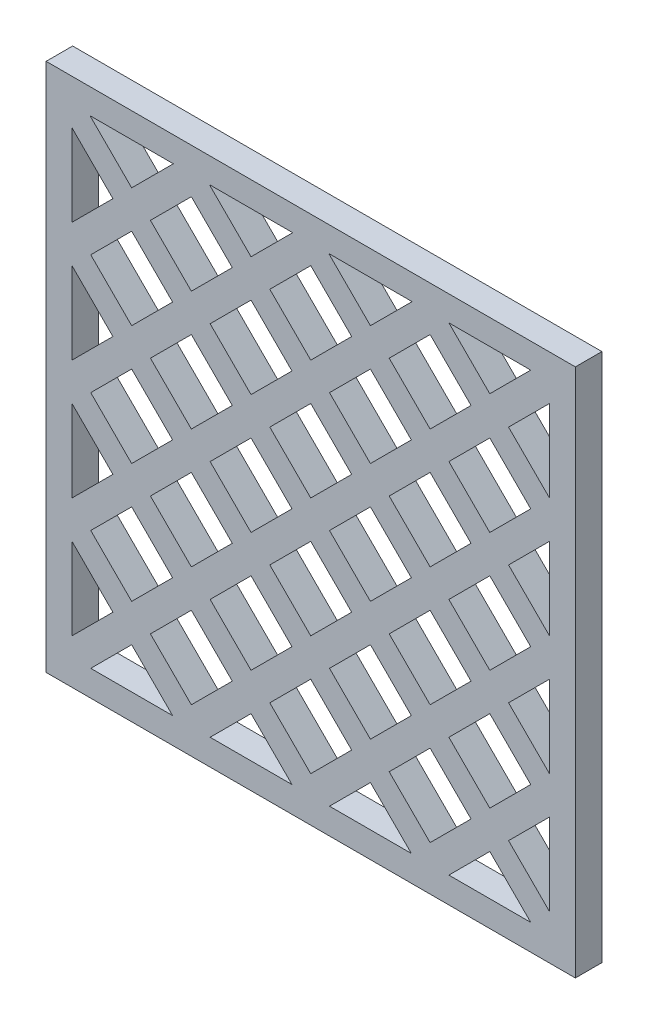
SolidWorks part; units mm, degrees
ref_plane "Front Plane" through (0, 0, 0) normal (0, 0, 1) x (1, 0, 0)
ref_plane "Top Plane" through (0, 0, 0) normal (0, 1, 0) x (1, 0, 0)
ref_plane "Right Plane" through (0, 0, 0) normal (1, 0, 0) x (0, 0, -1)
sketch "Sketch4" plane through (0, 0, 0) normal (0, 0, 1) x (1, 0, 0)
  line L0 (-16.7778, -18) -> (-10.4142, -18) construction
  line L1 (-16.6426, 18.0568) -> (-10.3574, 18.0568)
  line L2 (-18, 16.5858) -> (-18, 10.4142)
  line L3 (-16.7778, -18) -> (-10.4142, -18)
  line L5 (10.4142, -18) -> (16.5858, -18)
  line L6 (-18, -18) -> (0, 0) construction
  line L7 (-9, -18) -> (-9, -9) construction
  line L8 (-9, -9) -> (-18, -9) construction
  line L9 (-18, -10.4142) -> (-18, -16.7778) construction
  line L12 (-10.4142, -9) -> (-13.5, -12.0858)
  line L15 (-9, -10.4142) -> (-12.0858, -13.5)
  line L16 (-10.2222, -9) -> (-16.7778, -18) construction
  line L17 (-18, -16.7778) -> (-9, -10.2222) construction
  line L22 (-13.5, -13.5) -> (-13.5, -18) construction
  line L23 (-13.5, -18) -> (-13.5, -9) construction
  line L24 (-9, -13.5) -> (-18, -13.5) construction
  line L25 (-18, -13.5) -> (-13.5, -13.5) construction
  line L26 (-14.9142, -13.5) -> (-18, -16.5858)
  line L27 (-13.5, -14.9142) -> (-16.5858, -18)
  line L28 (-9, -16.5858) -> (-12.0858, -13.5)
  line L29 (-13.5, -14.9142) -> (-10.4142, -18)
  line L30 (-14.9142, -13.5) -> (-18, -10.4142)
  line L31 (-16.5858, -9) -> (-13.5, -12.0858)
  line L32 (-5.9142, -13.5) -> (-9, -10.4142)
  line L33 (-7.5858, -9) -> (-4.5, -12.0858)
  line L34 (-1.4142, -9) -> (-4.5, -12.0858)
  line L35 (0, -10.4142) -> (-3.0858, -13.5)
  line L36 (0, -16.5858) -> (-3.0858, -13.5)
  line L37 (-4.5, -14.9142) -> (-1.4142, -18)
  line L38 (-4.5, -14.9142) -> (-7.5858, -18)
  line L39 (-5.9142, -13.5) -> (-9, -16.5858)
  line L40 (3.0858, -13.5) -> (0, -10.4142)
  line L41 (1.4142, -9) -> (4.5, -12.0858)
  line L42 (7.5858, -9) -> (4.5, -12.0858)
  line L43 (9, -10.4142) -> (5.9142, -13.5)
  line L44 (9, -16.5858) -> (5.9142, -13.5)
  line L45 (4.5, -14.9142) -> (7.5858, -18)
  line L46 (4.5, -14.9142) -> (1.4142, -18)
  line L47 (3.0858, -13.5) -> (0, -16.5858)
  line L48 (12.0858, -13.5) -> (9, -10.4142)
  line L49 (10.4142, -9) -> (13.5, -12.0858)
  line L50 (16.5858, -9) -> (13.5, -12.0858)
  line L51 (18, -10.4142) -> (14.9142, -13.5)
  line L52 (18, -16.5858) -> (14.9142, -13.5)
  line L53 (13.5, -14.9142) -> (16.5858, -18)
  line L54 (13.5, -14.9142) -> (10.4142, -18)
  line L55 (12.0858, -13.5) -> (9, -16.5858)
  line L56 (-5.9142, -4.5) -> (-9, -1.4142)
  line L57 (-7.5858, 0) -> (-4.5, -3.0858)
  line L58 (-1.4142, 0) -> (-4.5, -3.0858)
  line L59 (0, -1.4142) -> (-3.0858, -4.5)
  line L60 (0, -7.5858) -> (-3.0858, -4.5)
  line L61 (-4.5, -5.9142) -> (-1.4142, -9)
  line L62 (-4.5, -5.9142) -> (-7.5858, -9)
  line L63 (-5.9142, -4.5) -> (-9, -7.5858)
  line L64 (3.0858, -4.5) -> (0, -1.4142)
  line L65 (1.4142, 0) -> (4.5, -3.0858)
  line L66 (7.5858, 0) -> (4.5, -3.0858)
  line L67 (9, -1.4142) -> (5.9142, -4.5)
  line L68 (9, -7.5858) -> (5.9142, -4.5)
  line L69 (4.5, -5.9142) -> (7.5858, -9)
  line L70 (4.5, -5.9142) -> (1.4142, -9)
  line L71 (3.0858, -4.5) -> (0, -7.5858)
  line L72 (12.0858, -4.5) -> (9, -1.4142)
  line L73 (10.4142, 0) -> (13.5, -3.0858)
  line L74 (16.5858, 0) -> (13.5, -3.0858)
  line L75 (18, -1.4142) -> (14.9142, -4.5)
  line L76 (18, -7.5858) -> (14.9142, -4.5)
  line L77 (13.5, -5.9142) -> (16.5858, -9)
  line L78 (13.5, -5.9142) -> (10.4142, -9)
  line L79 (12.0858, -4.5) -> (9, -7.5858)
  line L80 (-5.9142, 4.5) -> (-9, 7.5858)
  line L81 (-7.5858, 9) -> (-4.5, 5.9142)
  line L82 (-1.4142, 9) -> (-4.5, 5.9142)
  line L83 (0, 7.5858) -> (-3.0858, 4.5)
  line L84 (0, 1.4142) -> (-3.0858, 4.5)
  line L85 (-4.5, 3.0858) -> (-1.4142, 0)
  line L86 (-4.5, 3.0858) -> (-7.5858, 0)
  line L87 (-5.9142, 4.5) -> (-9, 1.4142)
  line L88 (3.0858, 4.5) -> (0, 7.5858)
  line L89 (1.4142, 9) -> (4.5, 5.9142)
  line L90 (7.5858, 9) -> (4.5, 5.9142)
  line L91 (9, 7.5858) -> (5.9142, 4.5)
  line L92 (9, 1.4142) -> (5.9142, 4.5)
  line L93 (4.5, 3.0858) -> (7.5858, 0)
  line L94 (4.5, 3.0858) -> (1.4142, 0)
  line L95 (3.0858, 4.5) -> (0, 1.4142)
  line L96 (12.0858, 4.5) -> (9, 7.5858)
  line L97 (10.4142, 9) -> (13.5, 5.9142)
  line L98 (16.5858, 9) -> (13.5, 5.9142)
  line L99 (18, 7.5858) -> (14.9142, 4.5)
  line L100 (18, 1.4142) -> (14.9142, 4.5)
  line L101 (13.5, 3.0858) -> (16.5858, 0)
  line L102 (13.5, 3.0858) -> (10.4142, 0)
  line L103 (12.0858, 4.5) -> (9, 1.4142)
  line L104 (-5.9142, 13.5) -> (-9, 16.5858)
  line L105 (-7.6426, 18.0568) -> (-4.5, 14.9142)
  line L106 (-1.3574, 18.0568) -> (-4.5, 14.9142)
  line L107 (0, 16.5858) -> (-3.0858, 13.5)
  line L108 (0, 10.4142) -> (-3.0858, 13.5)
  line L109 (-4.5, 12.0858) -> (-1.4142, 9)
  line L110 (-4.5, 12.0858) -> (-7.5858, 9)
  line L111 (-5.9142, 13.5) -> (-9, 10.4142)
  line L112 (3.0858, 13.5) -> (0, 16.5858)
  line L113 (1.3574, 18.0568) -> (4.5, 14.9142)
  line L114 (7.6426, 18.0568) -> (4.5, 14.9142)
  line L115 (9, 16.5858) -> (5.9142, 13.5)
  line L116 (9, 10.4142) -> (5.9142, 13.5)
  line L117 (4.5, 12.0858) -> (7.5858, 9)
  line L118 (4.5, 12.0858) -> (1.4142, 9)
  line L119 (3.0858, 13.5) -> (0, 10.4142)
  line L120 (12.0858, 13.5) -> (9, 16.5858)
  line L121 (10.4142, 18.0568) -> (13.5, 14.9711)
  line L122 (16.5858, 18.0568) -> (13.5, 14.9711)
  line L125 (13.5, 12.0858) -> (16.5858, 9)
  line L126 (13.5, 12.0858) -> (10.4142, 9)
  line L127 (12.0858, 13.5) -> (9, 10.4142)
  line L128 (-14.9142, -4.5) -> (-18, -1.4142)
  line L129 (-16.5858, 0) -> (-13.5, -3.0858)
  line L130 (-10.4142, 0) -> (-13.5, -3.0858)
  line L131 (-9, -1.4142) -> (-12.0858, -4.5)
  line L132 (-9, -7.5858) -> (-12.0858, -4.5)
  line L133 (-13.5, -5.9142) -> (-10.4142, -9)
  line L134 (-13.5, -5.9142) -> (-16.5858, -9)
  line L135 (-14.9142, -4.5) -> (-18, -7.5858)
  line L136 (-14.9142, 4.5) -> (-18, 7.5858)
  line L137 (-16.5858, 9) -> (-13.5, 5.9142)
  line L138 (-10.4142, 9) -> (-13.5, 5.9142)
  line L139 (-9, 7.5858) -> (-12.0858, 4.5)
  line L140 (-9, 1.4142) -> (-12.0858, 4.5)
  line L141 (-13.5, 3.0858) -> (-10.4142, 0)
  line L142 (-13.5, 3.0858) -> (-16.5858, 0)
  line L143 (-14.9142, 4.5) -> (-18, 1.4142)
  line L144 (-14.9142, 13.5) -> (-18, 16.5858)
  line L145 (-16.6426, 18.0568) -> (-13.5, 14.9142)
  line L146 (-10.3574, 18.0568) -> (-13.5, 14.9142)
  line L147 (-9, 16.5858) -> (-12.0858, 13.5)
  line L148 (-9, 10.4142) -> (-12.0858, 13.5)
  line L149 (-13.5, 12.0858) -> (-10.4142, 9)
  line L150 (-13.5, 12.0858) -> (-16.5858, 9)
  line L151 (-14.9142, 13.5) -> (-18, 10.4142)
  line L152 (-18, 10.4142) -> (-18, 16.5858)
  line L153 (-16.6426, 18.0568) -> (-10.3574, 18.0568)
  line L154 (-7.6426, 18.0568) -> (-1.3574, 18.0568)
  line L155 (1.3574, 18.0568) -> (7.6426, 18.0568)
  line L156 (10.4142, 18.0568) -> (16.5858, 18.0568)
  line L158 (18, 7.5858) -> (18, 1.4142)
  line L159 (18, -1.4142) -> (18, -7.5858)
  line L160 (18, -10.4142) -> (18, -16.5858)
  line L161 (0, 0) -> (16.5858, 0) construction
  line L162 (10.4142, -18) -> (16.5858, -18)
  line L163 (7.5858, -18) -> (1.4142, -18)
  line L164 (-1.4142, -18) -> (-7.5858, -18)
  line L165 (-10.4142, -18) -> (-16.7778, -18)
  line L166 (-18, -16.5858) -> (-18, -10.4142)
  line L167 (-16.5858, -18) -> (-10.4142, -18)
  line L168 (-18, -7.5858) -> (-18, -1.4142)
  line L169 (-18, 1.4142) -> (-18, 7.5858)
  line L170 (-18, 7.5858) -> (-18, 1.4142)
  line L171 (-7.6426, 18.0568) -> (-1.3574, 18.0568)
  line L172 (1.3574, 18.0568) -> (7.6426, 18.0568)
  line L173 (10.4142, 18.0568) -> (16.5858, 18.0568)
  line L174 (18, 7.5858) -> (18, 1.4142)
  line L175 (18, -10.4142) -> (18, -16.5858)
  line L176 (1.4142, -18) -> (7.5858, -18)
  line L177 (-7.5858, -18) -> (-1.4142, -18)
  line L178 (-18, -10.4142) -> (-18, -16.7778)
  line L179 (-18, -1.4142) -> (-18, -7.5858)
  line L180 (18, 16.5858) -> (18, 10.4142)
  line L181 (18, 10.4142) -> (14.9142, 13.5)
  line L182 (18, 16.5858) -> (14.9142, 13.5)
  point P0 (0, 0)
  dimension "D1" = 4.364
  dimension "D2" = 2
  dimension "D3" = 1
  dimension "D4" = 6.1716
  dimension "D5" = 1
sketch "Sketch5" plane through (0, 0, 0) normal (0, 0, 1) x (1, 0, 0)
  line L1 (-20, 20) -> (20, 20)
  line L2 (-20, 20) -> (-20, -20)
  line L3 (-20, -20) -> (20, -20)
  line L4 (20, 20) -> (20, -20)
  line L5 (-20, 20) -> (20, -20) construction
  line L6 (-20, -20) -> (20, 20) construction
  point P0 (0, 0)
  dimension "D1" = 40
  dimension "D2" = 40
extrude "Boss-Extrude2" add sketch "Sketch5" along normal blind 2
extrude "Cut-Extrude1" cut sketch "Sketch4" along normal blind 2 contours L180 L182 L181 | L156 L121 L122 region at (13.5, 17.0283, 0) region at (16.9714, 13.5, 0)
extrude "Cut-Extrude4" cut sketch "Sketch4<5>" along normal blind 2 contours L29 L27 L3 | L39 L32 L15 L28 | L133 L134 L31 L12 | L166 L26 L30 region at (-13.5, -16.9714, 0) region at (-13.5, -9, 0) region at (-9, -13.5, 0) region at (-16.9714, -13.5, 0)
sketch "Sketch4<5>" plane through (0, 0, 0) normal (0, 0, 1) x (1, 0, 0) same geometry as "Sketch4"
extrude "Cut-Extrude5" cut sketch "Sketch4<6>" along normal blind 2 contours L164 L37 L38 | L47 L40 L35 L36 | L163 L45 L46 | L55 L48 L43 L44 | L53 L54 L5 | L160 L51 L52 | L77 L78 L49 L50 | L69 L70 L41 L42 | L79 L72 L67 L68 | L159 L75 L76 region at (13.5, -16.9714, 0) region at (0, -13.5, 0) region at (-4.5, -16.9714, 0) region at (4.5, -9, 0) region at (9, -13.5, 0) region at (4.5, -16.9714, 0) region at (13.5, -9, 0) region at (16.9714, -13.5, 0) region at (9, -4.5, 0) region at (16.9714, -4.5, 0)
sketch "Sketch4<6>" plane through (0, 0, 0) normal (0, 0, 1) x (1, 0, 0) same geometry as "Sketch4"
extrude "Cut-Extrude6" cut sketch "Sketch4<7>" along normal blind 2 contours L101 L102 L73 L74 | L158 L99 L100 | L125 L126 L97 L98 | L103 L96 L91 L92 | L117 L118 L89 L90 | L127 L120 L115 L116 | L155 L113 L114 | L119 L112 L107 L108 | L95 L88 L83 L84 | L93 L94 L65 L66 | L71 L64 L59 L60 | L61 L62 L33 L34 region at (-4.5, -9, 0) region at (0, -4.5, 0) region at (4.5, 0, 0) region at (13.5, 0, 0) region at (0, 4.5, 0) region at (4.5, 9, 0) region at (9, 4.5, 0) region at (13.5, 9, 0) region at (16.9714, 4.5, 0) region at (0, 13.5, 0) region at (4.5, 17.0093, 0) region at (9, 13.5, 0)
sketch "Sketch4<7>" plane through (0, 0, 0) normal (0, 0, 1) x (1, 0, 0) same geometry as "Sketch4"
extrude "Cut-Extrude7" cut sketch "Sketch4<9>" along normal blind 2 contours L140 L87 L80 L139 | L85 L86 L57 L58 | L132 L63 L56 L131 | L141 L142 L129 L130 | L168 L135 L128 | L169 L143 L136 region at (-9, -4.5, 0) region at (-4.5, 0, 0) region at (-9, 4.5, 0) region at (-16.9714, -4.5, 0) region at (-13.5, 0, 0) region at (-16.9714, 4.5, 0)
sketch "Sketch4<9>" plane through (0, 0, 0) normal (0, 0, 1) x (1, 0, 0) same geometry as "Sketch4"
extrude "Cut-Extrude8" cut sketch "Sketch4<10>" along normal blind 2 contours L109 L110 L81 L82 | L148 L111 L104 L147 | L149 L150 L137 L138 | L151 L144 L2 | L146 L1 L145 | L154 L105 L106 region at (-13.5, 17.0093, 0) region at (-16.9714, 13.5, 0) region at (-4.5, 9, 0) region at (-9, 13.5, 0) region at (-4.5, 17.0093, 0) region at (-13.5, 9, 0)
sketch "Sketch4<10>" plane through (0, 0, 0) normal (0, 0, 1) x (1, 0, 0) same geometry as "Sketch4"
sketch "Sketch6" plane through (0, 0, 0) normal (0, 0, -1) x (-1, 0, 0)
  line L14 (-19.95, -19.95) -> (19.95, -19.95)
  line L15 (19.95, -19.95) -> (19.95, 19.95)
  line L16 (-19.95, 19.95) -> (-19.95, -19.95)
  line L17 (19.95, 19.95) -> (-19.95, 19.95)
  line L18 (-19.95, -19.95) -> (19.95, -19.95)
  line L19 (19.95, -19.95) -> (19.95, 19.95)
  line L20 (-19.95, 19.95) -> (-19.95, -19.95)
  line L21 (19.95, 19.95) -> (-19.95, 19.95)
  dimension "D1" = 0.05
extrude "Cut-Extrude9" cut sketch "Sketch6" against normal blind 10 flip side to cut
